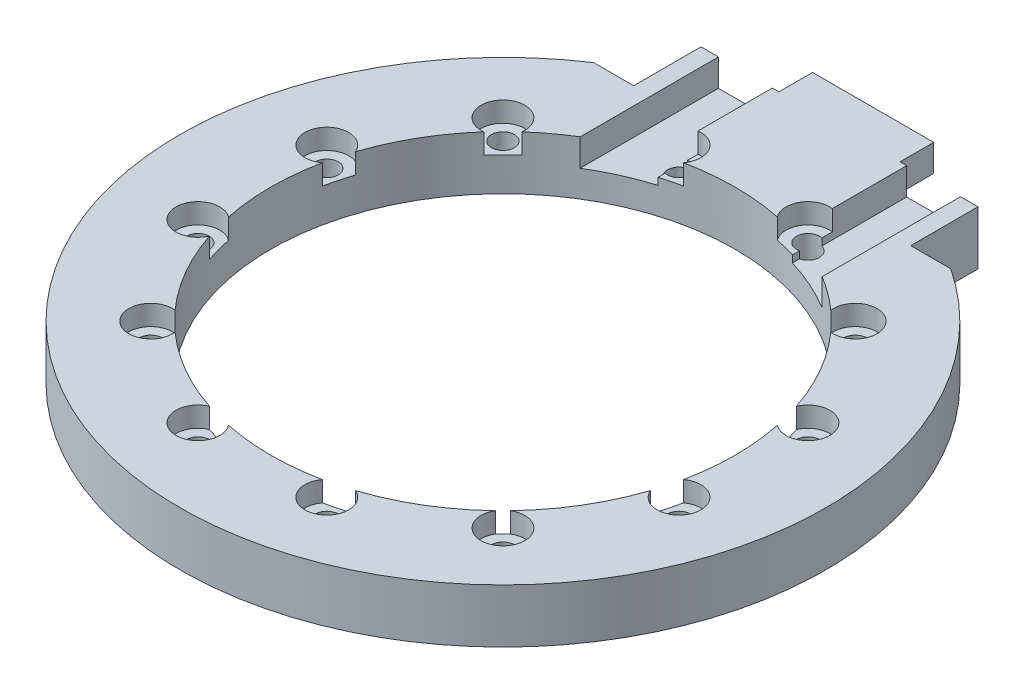
SolidWorks part; units mm, degrees
ref_plane "前视基准面" through (0, 0, 0) normal (0, 0, 1) x (1, 0, 0)
ref_plane "上视基准面" through (0, 0, 0) normal (0, 1, 0) x (1, 0, 0)
ref_plane "右视基准面" through (0, 0, 0) normal (1, 0, 0) x (0, 0, -1)
sketch "草图1" plane through (0, 0, 0) normal (0, 0, 1) x (1, 0, 0)
  circle A3 centre (0, 0) radius 26.5
extrude "凸台-拉伸1" add sketch "草图1" along normal blind 5
hole_wizard "M4 六角凹头盖的柱孔1" positions "3D草图2" profile "草图3" counterbore size "M4" standard "BSI" end condition through all
sketch3d "3D草图2"
  point P14 (-13.9806, 16.6615, 0)
  point P34 (-13.9806, 16.6615, 5)
  point P36 (13.9806, 16.6615, 5)
  point P38 (-21.75, 0, 5)
  point P40 (-13.9806, -16.6615, 5)
  point P42 (13.9806, -16.6615, 5)
  point P44 (21.75, 0, 5)
sketch "草图3" plane through (21.75, 0, 5) normal (1, 0, 0) x (0, -1, 0)
  line L0 (0, 0) -> (0, 5)
  line L1 (0, 5) -> (2.25, 5)
  line L3 (2.25, 5) -> (2.25, 4)
  line L4 (2.25, 4) -> (4, 4)
  line L5 (4, 4) -> (4, 0)
  line L7 (4, 0) -> (0, 0)
  line L11 (0, -6.35) -> (0, 107.95) construction
  dimension "通孔孔直径" = 4.5
  dimension "通孔孔深度" = 5
  dimension "柱形沉头孔直径" = 8
  dimension "柱形沉头孔深度" = 4
ref_plane "基准面1" through (0, 0, 5) normal (0, 0, 1) x (1, 0, 0)
sketch "参考" plane through (0, 0, 5) normal (0, 0, 1) x (1, 0, 0)
  line L12 (-20.7304, 8.7) -> (19.3146, 8.7) construction
ref_plane "基准面3" through (0, 8.7, 0) normal (0, -1, 0) x (1, 0, 0)
sketch "草图5" plane through (0, 8.7, 0) normal (0, -1, 0) x (1, 0, 0)
  line L0 (-26.5, 5) -> (-26.5, 14.9781)
  line L4 (26.5, 5) -> (26.5, 14.9781)
  line L9 (-26.5, 5) -> (26.5, 5)
  arc A4 (26.5, 14.9781) -> (-26.5, 14.9781) centre (0, 55) ccw
extrude "盘面" add sketch "草图5" against normal blind 8
sketch "草图6" plane through (0, 0, 5) normal (0, 0, 1) x (1, 0, 0)
  line L2 (-17.9806, 12.6615) -> (-9.9806, 12.6615)
  line L8 (-17.9806, 16.7) -> (-17.9806, 12.6615)
  line L9 (48, 16.7) -> (-48, 16.7) construction
  line L10 (-9.9806, 12.6615) -> (-9.9808, 16.7)
  line L11 (-9.9808, 16.7) -> (-17.9806, 16.7)
  line L14 (9.9808, 16.7) -> (17.9806, 16.7)
  line L15 (9.9806, 12.6615) -> (9.9808, 16.7)
  line L16 (17.9806, 16.7) -> (17.9806, 12.6615)
  line L17 (17.9806, 12.6615) -> (9.9806, 12.6615)
extrude "螺孔" cut sketch "草图6" along normal blind 22
sketch "草图8" plane through (0, 8.7, 0) normal (0, -1, 0) x (1, 0, 0)
  circle A1 centre (0, 55) radius 34.5
extrude "盘面切割" cut sketch "草图8" against normal through all
hole_wizard "M3 六角凹头盖的柱孔1" positions "3D草图3" profile "草图10" counterbore size "M3" standard "BSI" end condition through all
sketch3d "3D草图3"
  line L0 (0, 16.7, 55) -> (0, 12.6615, 55) construction
  line L5 (0, 16.7, 55) -> (9.5763, 16.7, 19.2607)
  line L7 (0, 16.7, 55) -> (-9.5763, 16.7, 90.7393)
  line L11 (26.163, 16.7, 28.837) -> (0, 16.7, 55)
  line L17 (35.7393, 16.7, 45.4237) -> (0, 16.7, 55)
  line L19 (0, 16.7, 55) -> (35.7393, 16.7, 64.5763)
  line L21 (0, 16.7, 55) -> (26.6194, 16.7, 81.6194)
  line L22 (0, 16.7, 55) -> (-26.163, 16.7, 28.837)
  line L37 (0, 16.7, 55) -> (9.5763, 16.7, 90.7393)
  line L44 (-9.5763, 16.7, 19.2607) -> (0, 16.7, 55)
  line L54 (0, 16.7, 55) -> (-35.7393, 16.7, 45.4237)
  line L56 (0, 16.7, 55) -> (-26.163, 16.7, 81.163)
  line L68 (0, 16.7, 55) -> (-35.7393, 16.7, 64.5763)
  point P19 (9.5763, 16.7, 19.2607)
  point P34 (26.163, 16.7, 28.837)
  point P43 (35.7393, 16.7, 45.4237)
  point P46 (35.7393, 16.7, 64.5763)
  point P49 (26.6194, 16.7, 81.6194)
  point P169 (9.5763, 16.7, 90.7393)
  point P171 (-9.5763, 16.7, 90.7393)
  point P173 (-26.163, 16.7, 81.163)
  point P181 (-26.163, 16.7, 28.837)
  point P183 (-35.7393, 16.7, 45.4237)
  point P185 (-35.7393, 16.7, 64.5763)
  point P187 (-9.5763, 16.7, 19.2607)
sketch "草图10" plane through (-9.5763, 16.7, 19.2607) normal (1, 0, 0) x (0, 0, 1)
  line L0 (0, 0) -> (0, 43.2)
  line L1 (0, 43.2) -> (1.7, 43.2)
  line L3 (1.7, 43.2) -> (1.7, 3)
  line L4 (1.7, 3) -> (3.25, 3)
  line L5 (3.25, 3) -> (3.25, 0)
  line L7 (3.25, 0) -> (0, 0)
  line L11 (0, -6.35) -> (0, 107.95) construction
  dimension "通孔孔直径" = 3.4
  dimension "通孔孔深度" = 43.2
  dimension "柱形沉头孔直径" = 6.5
  dimension "柱形沉头孔深度" = 3
sketch "草图11" plane through (0, 0, 0) normal (0, 0, 1) x (1, 0, 0)
  line L0 (-25.0312, 8.7) -> (-29.0312, 8.7)
  line L1 (-19.36, 8.7) -> (19.36, 8.7) construction
  line L2 (-29.0312, 8.7) -> (-29.0312, 16.7)
  line L3 (48, 16.7) -> (-48, 16.7) construction
  line L4 (-29.0312, 16.7) -> (-20.5757, 16.7)
  line L5 (-20.5757, 16.7) -> (-20.5757, 8.7)
  line L9 (-20.7304, 8.7) -> (19.3146, 8.7) construction
  line L10 (-20.5757, 8.7) -> (-25.0312, 8.7)
  line L12 (20.5757, 8.7) -> (25.0312, 8.7)
  line L13 (20.5757, 16.7) -> (20.5757, 8.7)
  line L14 (29.0312, 16.7) -> (20.5757, 16.7)
  line L15 (29.0312, 8.7) -> (29.0312, 16.7)
  line L16 (25.0312, 8.7) -> (29.0312, 8.7)
  arc A0 (-25.0312, 8.7) -> (25.0312, 8.7) centre (0, 0) ccw construction
extrude "切除-拉伸1" cut sketch "草图11" along normal blind 15
sketch "草图12" plane through (0, 8.7, 0) normal (0, -1, 0) x (1, 0, 0)
  line L2 (39.2995, 79.0331) -> (30.6404, 73.9927)
  line L3 (40.2995, 32.8878) -> (31.6288, 37.8938)
  line L5 (25.4094, 16.6939) -> (19.8988, 25.0014)
  line L6 (39.2995, 31.1557) -> (30.6288, 36.1618)
  line L7 (31.6038, 72.2393) -> (40.2207, 77.2552)
  line L9 (-1, 96.0328) -> (-1, 90.9861)
  line L10 (1, 96.0328) -> (1, 101.0547)
  line L11 (1, 96.0328) -> (1, 90.9861)
  line L12 (-1, 96.0328) -> (-1, 101.0547)
  line L13 (-31.6038, 72.2393) -> (-40.2207, 77.2552)
  line L14 (-39.2995, 31.1557) -> (-30.6288, 36.1618)
  line L15 (-25.4094, 16.6939) -> (-19.8988, 25.0014)
  line L16 (-40.2995, 32.8878) -> (-31.6288, 37.8938)
  line L17 (-39.2995, 79.0331) -> (-30.6404, 73.9927)
  arc A9 (27.8489, 77.813) -> (22.813, 82.849) centre (26.6194, 81.6194) ccw
  arc A13 (12.9499, 88.5902) -> (5.5801, 90.5649) centre (9.5763, 90.7393) ccw
  arc A14 (33.5513, 42.0651) -> (35.5645, 49.4283) centre (35.7393, 45.4237) ccw
  arc A15 (35.5633, 60.5798) -> (33.59, 67.9502) centre (35.7393, 64.5763) ccw
  arc A16 (22.6075, 26.986) -> (27.9776, 32.4112) centre (26.163, 28.837) ccw
  arc A17 (12.9499, 88.5902) -> (22.813, 82.849) centre (0, 55) cw
  arc A18 (33.59, 67.9502) -> (31.6038, 72.2393) centre (0, 55) ccw
  arc A19 (35.5633, 60.5798) -> (35.5645, 49.4283) centre (0, 55) cw
  arc A20 (30.6288, 36.1618) -> (27.9776, 32.4112) centre (0, 55) cw
  arc A21 (22.6075, 26.986) -> (19.8988, 25.0014) centre (0, 55) cw
  arc A22 (5.5801, 90.5649) -> (1, 90.9861) centre (0, 55) ccw
  arc A23 (25.4094, 16.6939) -> (39.2995, 31.1557) centre (0, 55) ccw
  arc A24 (31.6288, 37.8938) -> (33.5513, 42.0651) centre (0, 55) ccw
  arc A25 (40.2995, 32.8878) -> (40.2207, 77.2552) centre (0, 55) ccw
  arc A26 (39.2995, 79.0331) -> (1, 101.0547) centre (0, 55) ccw
  arc A27 (30.6404, 73.9927) -> (27.8992, 77.8296) centre (0, 55) ccw
  arc A28 (-30.6404, 73.9927) -> (-27.8992, 77.8296) centre (0, 55) cw
  arc A29 (-39.2995, 79.0331) -> (-1, 101.0547) centre (0, 55) cw
  arc A30 (-40.2995, 32.8878) -> (-40.2207, 77.2552) centre (0, 55) cw
  arc A31 (-31.6288, 37.8938) -> (-33.5513, 42.0651) centre (0, 55) cw
  arc A32 (-25.4094, 16.6939) -> (-39.2995, 31.1557) centre (0, 55) cw
  arc A33 (-5.5801, 90.5649) -> (-1, 90.9861) centre (0, 55) cw
  arc A34 (-22.6075, 26.986) -> (-19.8988, 25.0014) centre (0, 55) ccw
  arc A35 (-30.6288, 36.1618) -> (-27.9776, 32.4112) centre (0, 55) ccw
  arc A36 (-35.5633, 60.5798) -> (-35.5645, 49.4283) centre (0, 55) ccw
  arc A37 (-33.59, 67.9502) -> (-31.6038, 72.2393) centre (0, 55) cw
  arc A38 (-12.9499, 88.5902) -> (-22.813, 82.849) centre (0, 55) ccw
  arc A39 (-22.6075, 26.986) -> (-27.9776, 32.4112) centre (-26.163, 28.837) cw
  arc A40 (-35.5633, 60.5798) -> (-33.59, 67.9502) centre (-35.7393, 64.5763) cw
  arc A41 (-33.5513, 42.0651) -> (-35.5645, 49.4283) centre (-35.7393, 45.4237) cw
  arc A42 (-12.9499, 88.5902) -> (-5.5801, 90.5649) centre (-9.5763, 90.7393) cw
  arc A43 (-27.8489, 77.813) -> (-22.813, 82.849) centre (-26.6194, 81.6194) cw
extrude "切除-拉伸2" cut sketch "草图12" against normal blind 5 contours A27 L2 A26 L10 L11 A22 A13 A17 A9 | L3 A25 L7 A18 A15 A19 A14 A24 | L5 A23 L6 A20 A16 A21 | A28 A43 A38 A42 A33 L9 L12 A29 L17 | A31 A41 A36 A40 A37 L13 A30 L16 | A34 A39 A35 L14 A32 L15 region at (19.8462, 8.7, 89.8632) region at (40.0107, 8.7, 55.079) region at (30.014, 8.7, 26.342) region at (-19.8462, 8.7, 89.8632) region at (-40.0107, 8.7, 55.079) region at (-30.014, 8.7, 26.342)
sketch "草图13" plane through (0, 0, 5) normal (0, 0, 1) x (1, 0, 0)
  line L0 (-20.7304, 8.7) -> (19.3146, 8.7) construction
  line L1 (-12.2192, 8.7) -> (12.2192, 8.7)
  arc A1 (-12.2192, 8.7) -> (12.2192, 8.7) centre (0, 0) ccw
extrude "切除-拉伸3" cut sketch "草图13" against normal blind 10
sketch "草图14" plane through (0, 0, 5) normal (0, 0, 1) x (1, 0, 0)
  line L0 (-9, 16.7) -> (9, 16.7)
  line L1 (48, 16.7) -> (-48, 16.7) construction
  line L2 (0, 12.7) -> (-9, 12.7)
  line L3 (-9, 12.7) -> (-9, 16.7)
  line L5 (9, 16.7) -> (9, 12.7)
  line L6 (9, 12.7) -> (0, 12.7)
  circle A0 centre (0, 0) radius 26.5
extrude "切除-拉伸4" cut sketch "草图14" against normal blind 10
